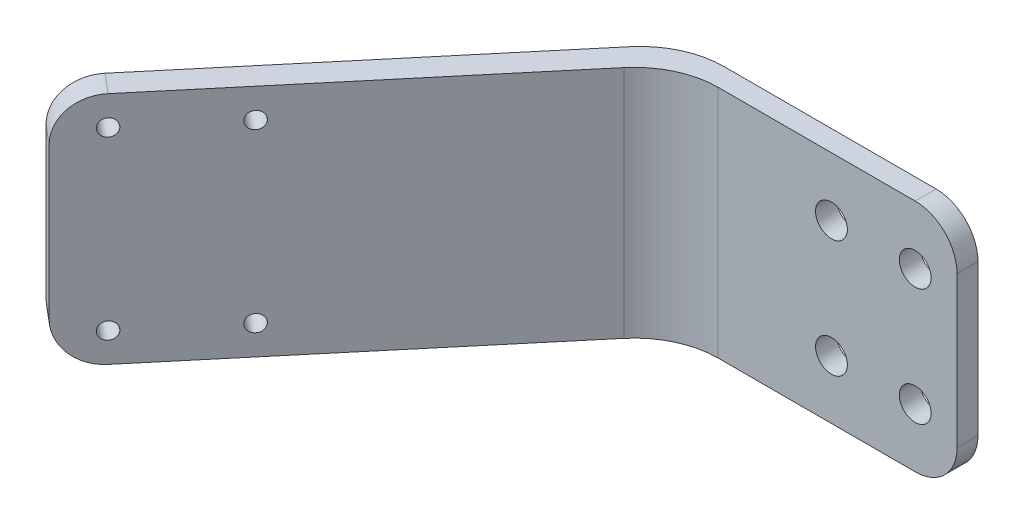
SolidWorks part; units mm, degrees
ref_plane "Front Plane" through (0, 0, 0) normal (0, 0, 1) x (1, 0, 0)
ref_plane "Top Plane" through (0, 0, 0) normal (0, 1, 0) x (1, 0, 0)
ref_plane "Right Plane" through (0, 0, 0) normal (1, 0, 0) x (0, 0, -1)
sketch "Sketch1" plane through (0, 0, 0) normal (0, 0, 1) x (1, 0, 0)
  line L5 (-178.1685, 63.1549) -> (-143.1685, 63.1549)
  line L6 (-178.1685, 63.1549) -> (-178.1685, 35.1549)
  line L7 (-178.1685, 35.1549) -> (-143.1685, 35.1549)
  line L8 (-143.1685, 63.1549) -> (-143.1685, 35.1549)
  line L9 (-178.1685, 63.1549) -> (-143.1685, 35.1549) construction
  line L10 (-178.1685, 35.1549) -> (-143.1685, 63.1549) construction
  point P0 (-160.6685, 49.1549)
  dimension "D1" = 28
  dimension "D2" = 35
extrude "Boss-Extrude1" add sketch "Sketch1" against normal blind 2.5
sketch "Sketch3" plane through (0, 35.1549, 0) normal (0, -1, 0) x (1, 0, 0)
  line L0 (-178.1685, -2.5) -> (-212.974, 38.9796)
  line L1 (-178.1685, -2.5) -> (-178.1685, 0) construction
  line L2 (-178.1685, -2.5) -> (-143.1685, -2.5) construction
  line L3 (-175.3012, -1.25) -> (-210.6759, 40.908)
  line L4 (-212.974, 38.9796) -> (-210.6759, 40.908)
  line L5 (-178.1685, -2.5) -> (-143.1685, -2.5)
  line L6 (-143.1685, -2.5) -> (-143.1685, -1.25)
  line L7 (-143.1685, -2.5) -> (-143.1685, 0) construction
  line L8 (-143.1685, -1.25) -> (-175.3012, -1.25)
  line L9 (-175.8704, -0.5716) -> (-210.6759, 40.908) construction
  dimension "D1" = 130
  dimension "D2" = 3
extrude "Boss-Extrude2" add sketch "Sketch3" against normal up to surface (28 mm away) up to face at (-160.6685, 63.1549, -1.25)
sketch "Sketch5" plane through (-103.4865, 0, -86.8354) normal (0.766, 0, 0.6428) x (0.6428, 0, -0.766)
  line L3 (-166.7572, 63.1549) -> (-166.7572, 35.1549) construction
  line L4 (-113.3556, 63.1549) -> (-166.7572, 63.1549) construction
  line L6 (-141.2023, 38.6549) -> (-116.2818, 38.6549)
  line L7 (-141.2023, 38.6549) -> (-141.2023, 59.6549)
  line L8 (-141.2023, 59.6549) -> (-116.2818, 59.6549)
  line L9 (-116.2818, 38.6549) -> (-116.2818, 59.6549)
  circle A0 centre (-161.7572, 59.6549) radius 1
  circle A1 centre (-161.7572, 38.6549) radius 1
  circle A2 centre (-149.2572, 59.6549) radius 1
  circle A3 centre (-149.2572, 38.6549) radius 1
  point P14 (0, 0)
  point P17 (0, 0)
  dimension "D1" = 5
  dimension "D2" = 3.5
  dimension "D3" = 21
  dimension "D4" = 12.5
  dimension "D5" = 21
extrude "Cut-Extrude2" cut sketch "Sketch5" against normal blind 10 contours A1 | A0 | A2 | A3 region at (-207.4619, 59.6549, 37.0777) region at (-207.4619, 38.6549, 37.0777) region at (-199.4271, 59.6549, 27.5022) region at (-199.4271, 38.6549, 27.5022)
sketch "Sketch2" plane through (0, 0, 0) normal (0, 0, 1) x (1, 0, 0)
  line L0 (-143.1685, 35.1549) -> (-143.1685, 63.1549) construction
  line L2 (-143.1685, 63.1549) -> (-176.35, 63.1549) construction
  line L5 (-171.1685, 35.1549) -> (-171.1685, 63.1549) construction
  line L6 (-171.1685, 63.1549) -> (-171.1685, 35.1549) construction
  circle A0 centre (-148.1685, 56.1549) radius 1.9
  circle A1 centre (-148.1685, 42.1549) radius 1.9
  circle A2 centre (-158.1685, 42.1549) radius 1.9
  circle A3 centre (-158.1685, 56.1549) radius 1.9
  point P24 (0, 0)
  point P30 (0, 0)
  dimension "D1" = 14
  dimension "D3" = 3.8
  dimension "D4" = 3.8
  dimension "D5" = 3.8
  dimension "D6" = 3.8
  dimension "D2" = 10
  dimension "D7" = 5
  dimension "D8" = 10
extrude "Cut-Extrude1" cut sketch "Sketch2" against normal blind 75 contours A0 | A3 | A2 | A1 region at (-148.1685, 56.1549, 0) region at (-148.1685, 42.1549, 0) region at (-158.1685, 42.1549, 0) region at (-158.1685, 56.1549, 0)
fillet "Fillet1" radius 10 2 edges at (-178.1685, 49.1549, -2.5) (-176.35, 49.1549, 0)
fillet "Fillet2" radius 5 4 edges at (-143.1685, 35.1549, -1.25) (-143.1685, 63.1549, -1.25) (-211.825, 63.1549, 39.9438) (-211.825, 35.1549, 39.9438)
fillet "Fillet3" radius 2 rebuild error yes
